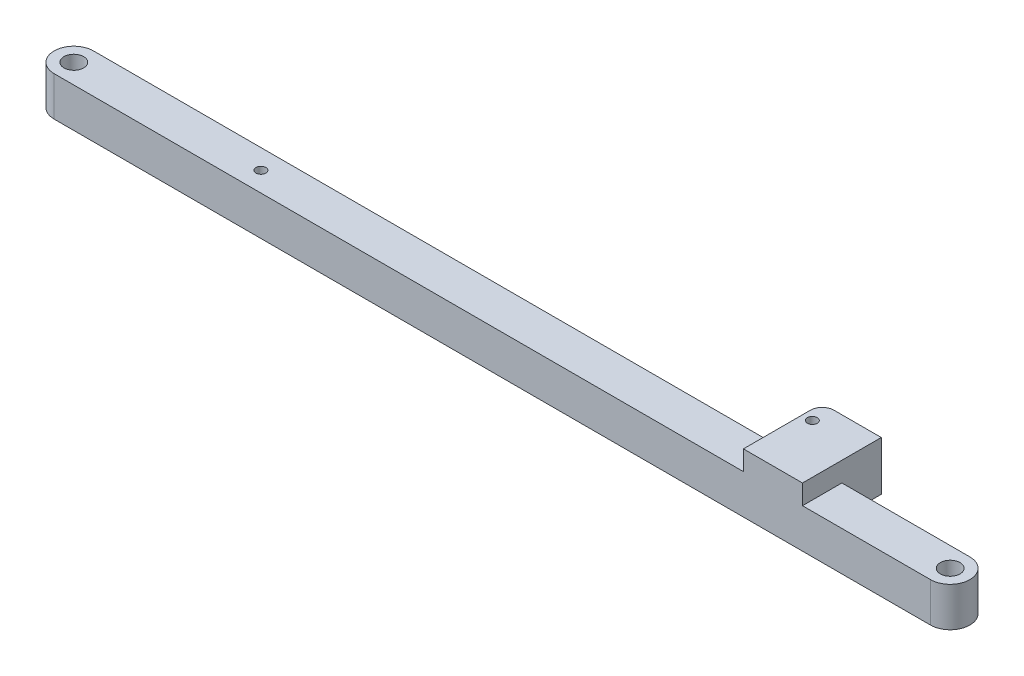
SolidWorks part; units mm, degrees
ref_plane "Front Plane" through (0, 0, 0) normal (0, 0, 1) x (1, 0, 0)
ref_plane "Top Plane" through (0, 0, 0) normal (0, 1, 0) x (1, 0, 0)
ref_plane "Right Plane" through (0, 0, 0) normal (1, 0, 0) x (0, 0, -1)
sketch "Sketch2" plane through (0, 0, 0) normal (0, 1, 0) x (1, 0, 0)
  line L0 (0, 0) -> (120.65, 0)
  line L1 (0, 0) -> (565.15, 0)
  line L2 (0, 0) -> (0, 25.4) construction
  line L3 (0, 25.4) -> (565.15, 25.4)
  line L4 (565.15, 0) -> (565.15, 25.4) construction
  line L5 (120.65, 0) -> (120.65, 25.4) construction
  circle A0 centre (120.65, 12.7) radius 12.7
  arc A1 (565.15, 25.4) -> (565.15, 0) centre (565.15, 12.7) cw
  circle A2 centre (120.65, 12.7) radius 3.175
  circle A3 centre (565.15, 12.7) radius 6.35
  arc A4 (0, 25.4) -> (0, 0) centre (0, 12.7) ccw
  circle A5 centre (0, 12.7) radius 6.35
  dimension "D4" = 6.35
  dimension "D5" = 12.7
  dimension "D6" = 12.7
  dimension "D1" = 565.15
  dimension "D2" = 25.4
  dimension "D3" = 120.65
extrude "Boss-Extrude1" add sketch "Sketch2" along normal blind 25.4 contours A0 L3 L2 L0 | A0 A2 | A1 L3 A0 L1 A3 region at (52.5215, 0, -12.7) region at (350.4658, 0, -12.7) region at (108.3092, 0, -12.7)
sketch "Sketch12" plane through (0, 0, -25.4) normal (0, 0, -1) x (-1, 0, 0)
  line L0 (-565.15, 25.4) -> (-482.6, 25.4)
  line L1 (0, 25.4) -> (-565.15, 25.4) construction
  line L2 (-482.6, 0) -> (-482.6, 38.1)
  line L3 (0, 0) -> (-565.15, 0) construction
  line L4 (-482.6, 38.1) -> (-444.5, 38.1)
  line L5 (-444.5, 38.1) -> (-444.5, 0)
  line L6 (-444.5, 0) -> (-482.6, 0)
  line L7 (-482.6, 6.35) -> (-444.5, 6.35)
  line L8 (-476.25, 12.7) -> (-444.5, 12.7)
  line L9 (-476.25, 31.75) -> (-444.5, 31.75)
  line L10 (-476.25, 12.7) -> (-476.25, 31.75)
  line M3 (0, 25.4) -> (-565.15, 25.4)
  dimension "D1" = 82.55
  dimension "D2" = 38.1
  dimension "D3" = 6.35
  dimension "D4" = 6.35
  dimension "D5" = 6.35
  dimension "D6" = 38.1
  dimension "D7" = 6.35
sketch "Sketch14" plane through (0, 25.4, 0) normal (0, 1, 0) x (1, 0, 0)
  line L0 (444.5, 25.4) -> (444.5, 0)
  line L1 (482.6, 25.4) -> (444.5, 25.4) construction
  line L2 (0, 0) -> (565.15, 0) construction
  line L3 (444.5, 0) -> (482.6, 0)
  line L4 (482.6, 0) -> (482.6, 25.4)
  line L5 (444.5, 25.4) -> (482.6, 25.4) construction
  line L6 (482.6, 25.4) -> (444.5, 25.4)
  line L7 (482.6, 25.4) -> (565.15, 25.4)
  line M2 (565.15, 25.4) -> (0, 25.4)
  line M4 (0, 0) -> (565.15, 0)
  dimension "D1" = 82.55
  dimension "D2" = 38.1
extrude "Boss-Extrude6" add sketch "Sketch14" along normal blind 12.7 contours L4 L0 M4 M2 region at (463.55, 25.4, -12.7)
extrude "Boss-Extrude7" add sketch "Sketch12" along normal blind 25.4 contours L10 L9 L5 L4 L2 M3 | L8 L10 L2 L7 L5 M3 region at (467.5187, 11.9063, -25.4) region at (465.8179, 34.0179, -25.4)
sketch "Sketch15" plane through (0, 6.35, 0) normal (0, -1, 0) x (1, 0, 0)
  line L0 (444.5, -38.1) -> (450.85, -38.1) construction
  line L1 (444.5, -50.8) -> (444.5, -25.4) construction
  circle A0 centre (450.85, -38.1) radius 3.175
  dimension "D2" = 6.35
  dimension "D1" = 6.35
extrude "Cut-Extrude3" cut sketch "Sketch15" against normal through all contours A0
fillet "Fillet1" radius 7.62 1 edges at (444.5, 9.525, -50.8)
